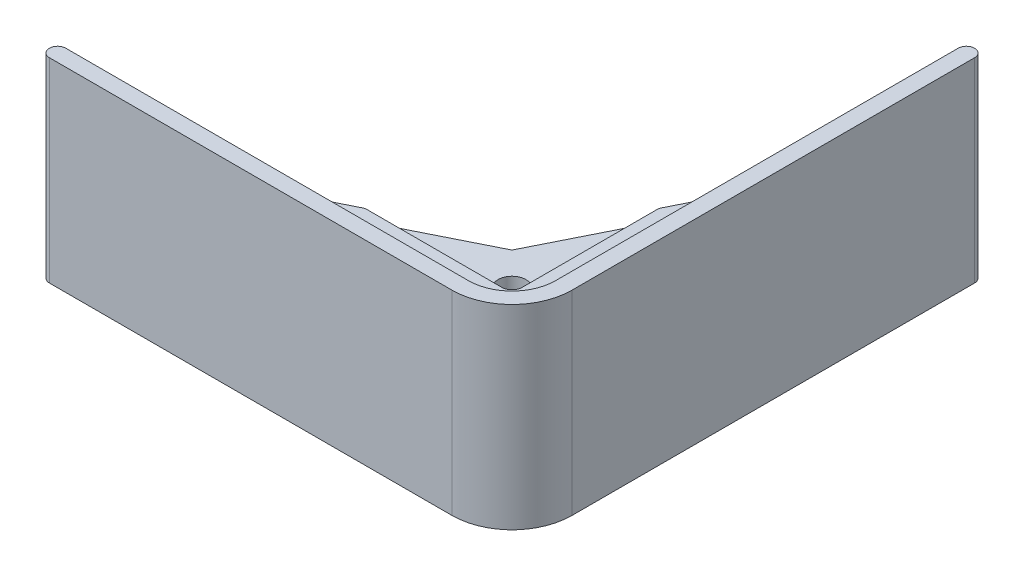
SolidWorks part; units mm, degrees
material "Nylon 101"
ref_plane "Front Plane" through (0, 0, 0) normal (0, 0, 1) x (1, 0, 0)
ref_plane "Top Plane" through (0, 0, 0) normal (0, 1, 0) x (1, 0, 0)
ref_plane "Right Plane" through (0, 0, 0) normal (1, 0, 0) x (0, 0, -1)
sketch "Sketch1" plane through (0, 0, 0) normal (0, 1, 0) x (1, 0, 0)
  line L0 (0, -18.542) -> (-127, -18.542)
  line L1 (18.542, 0) -> (18.542, 127)
  line L2 (-127, -18.542) -> (-127, -13.462)
  line L3 (-127, -13.462) -> (0, -13.462)
  line L4 (13.462, 0) -> (13.462, 127)
  line L5 (13.462, 127) -> (18.542, 127)
  line L6 (-6.0067, 12.0476) -> (-57.1711, -13.462)
  line L7 (-12.0476, 6.0067) -> (13.462, 57.1711)
  circle A0 centre (0, 0) radius 4.2862
  arc A1 (0, -18.542) -> (18.542, 0) centre (0, 0) ccw
  circle A2 centre (0, 0) radius 13.462
  dimension "D1" = 8.5725
  dimension "D4" = 5.08
  dimension "D5" = 127
  dimension "D6" = 26.5
  dimension "D3" = 13.462
extrude "Boss-Extrude1" add sketch "Sketch1" along normal blind 50.292 contours A2 L3 L2 L0 A1 L1 L5 L4 | A2 A0 | A2 L3 | A2 L4 L7 | A2 L6 L7 region at (-63.5, 0, 16.4837) region at (-26.4429, 0, 6.2746) region at (-11.1237, 0, 6.8835) region at (6.2746, 0, -26.4429) region at (-9.6262, 0, -9.6262)
fillet "Fillet2" radius 2.54 4 edges at (13.462, 25.146, -127) (18.542, 25.146, -127) (-127, 25.146, 13.462) (-127, 25.146, 18.542)
ref_plane "Plane1" through (0, 25.146, 0) normal (0, 1, 0) x (1, 0, 0)
sketch "Sketch7" plane through (0, 50.292, 0) normal (0, 1, 0) x (1, 0, 0)
  line L1 (5.08, -5.08) -> (-40.3594, -5.08)
  line L2 (5.08, -5.08) -> (5.08, 40.3594)
  line L3 (5.08, 40.3594) -> (-40.3594, 40.3594)
  line L4 (-40.3594, -5.08) -> (-40.3594, 40.3594)
  line L6 (-10.0378, 10.0378) -> (-57.1711, -13.462) construction
  circle A1 centre (0, 0) radius 4.2862 construction
  dimension "D1" = 5.08
  dimension "D2" = 5.08
extrude "Cut-Extrude3" cut sketch "Sketch7" against normal blind 3.556
fillet "Fillet9" radius 3.175 3 edges at (5.08, 48.514, -40.3594) (5.08, 48.514, 5.08) (-40.3594, 48.514, 5.08)
sketch "Sketch8" plane through (0, 25.146, 0) normal (0, 1, 0) x (1, 0, 0)
  line L0 (0, -13.462) -> (-124.46, -13.462)
  line L9 (-124.46, -18.542) -> (0, -18.542)
  line L10 (13.462, 57.1711) -> (5.4136, 41.0284)
  line L11 (5.08, 39.6118) -> (5.08, -1.905)
  line L12 (1.905, -5.08) -> (-39.6118, -5.08)
  line L13 (-41.0284, -5.4136) -> (-57.1711, -13.462)
  line L14 (-57.1711, -13.462) -> (-124.46, -13.462)
  line L16 (-124.46, -18.542) -> (0, -18.542)
  line L18 (18.542, 0) -> (18.542, 124.46)
  line L19 (13.462, 124.46) -> (13.462, 57.1711)
  line L29 (13.462, 124.46) -> (13.462, 0)
  line L30 (18.542, 0) -> (18.542, 124.46)
  arc A0 (0, -13.462) -> (13.462, 0) centre (0, 0) ccw
  arc A5 (-124.46, -13.462) -> (-127, -16.002) centre (-124.46, -16.002) ccw
  arc A7 (-124.46, -13.462) -> (-127, -16.002) centre (-124.46, -16.002) ccw
  arc A9 (5.4136, 41.0284) -> (5.08, 39.6118) centre (8.255, 39.6118) ccw
  arc A10 (1.905, -5.08) -> (5.08, -1.905) centre (1.905, -1.905) ccw
  arc A11 (-39.6118, -5.08) -> (-41.0284, -5.4136) centre (-39.6118, -8.255) ccw
  arc A16 (-127, -16.002) -> (-124.46, -18.542) centre (-124.46, -16.002) ccw
  arc A27 (-127, -16.002) -> (-124.46, -18.542) centre (-124.46, -16.002) ccw
  arc A29 (0, -18.542) -> (18.542, 0) centre (0, 0) ccw
  arc A31 (0, -18.542) -> (18.542, 0) centre (0, 0) ccw
  arc A32 (18.542, 124.46) -> (16.002, 127) centre (16.002, 124.46) ccw
  arc A33 (18.542, 124.46) -> (16.002, 127) centre (16.002, 124.46) ccw
  arc A34 (16.002, 127) -> (13.462, 124.46) centre (16.002, 124.46) ccw
  arc A35 (16.002, 127) -> (13.462, 124.46) centre (16.002, 124.46) ccw
  dimension "D1" = 0
extrude "Boss-Extrude2" add sketch "Sketch8" along normal mid plane 60.325
sketch "Sketch9" plane through (0, -5.0165, 0) normal (0, -1, 0) x (1, 0, 0)
  line L0 (-8.2875, 13.462) -> (7.112, 13.462)
  line L1 (-57.1711, 13.462) -> (0, 13.462) construction
  line L2 (13.462, -7.7751) -> (13.462, 7.112)
  line L3 (13.462, 0) -> (13.462, -57.1711) construction
  arc A0 (7.112, 13.462) -> (13.462, 7.112) centre (7.112, 7.112) cw
  arc A1 (13.462, 0) -> (0, 13.462) centre (0, 0) ccw construction
  arc A2 (13.462, 0) -> (0, 13.462) centre (0, 0) ccw
  point P9 (8.6874, 8.6874)
  arc M4 (0, 13.462) -> (13.462, 0) centre (0, 0) cw
  dimension "D1" = 6.35
extrude "Cut-Extrude4" cut sketch "Sketch9" along direction (0, 1, 0) on the side against the normal blind 4.7625 contours A0 L0 L2 M4 region at (10.0004, -5.0165, 10.0004)
equation "\"D1@Sketch1\"=.3125+0.025"
